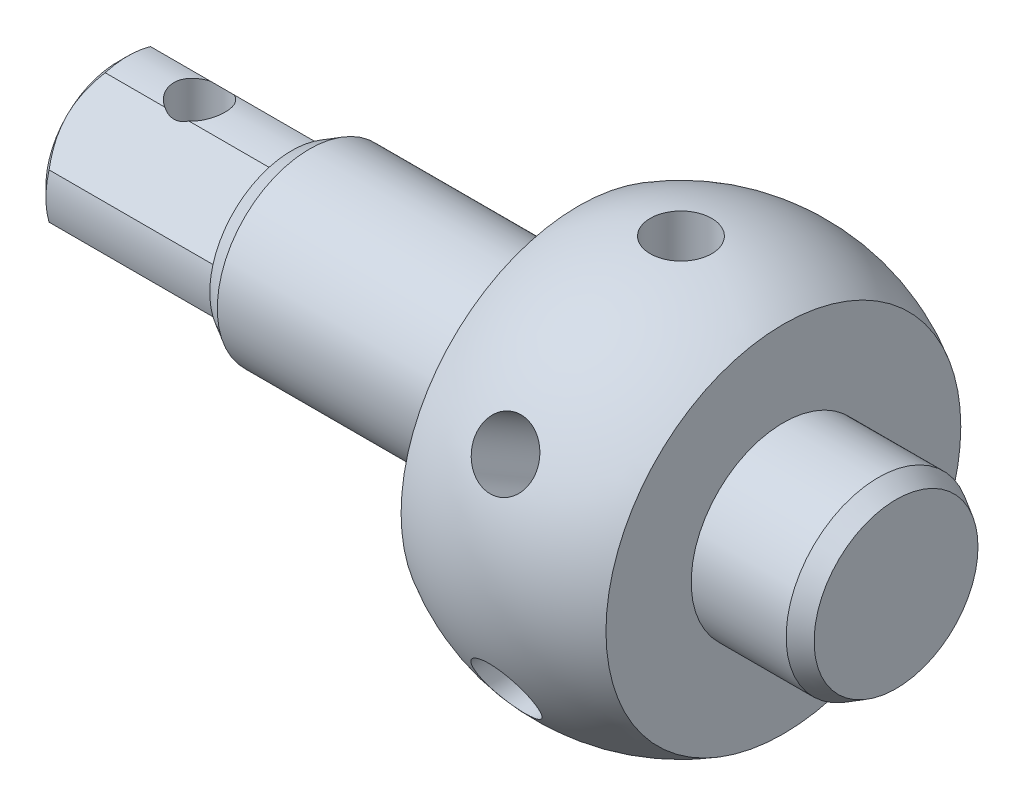
SolidWorks part; units mm, degrees
material "Простая углеродистая сталь"
ref_plane "Спереди" through (0, 0, 0) normal (0, 0, 1) x (1, 0, 0)
ref_plane "Сверху" through (0, 0, 0) normal (0, 1, 0) x (1, 0, 0)
ref_plane "Справа" through (0, 0, 0) normal (1, 0, 0) x (0, 0, -1)
sketch "Эскиз1" plane through (0, 0, 0) normal (0, 0, 1) x (1, 0, 0)
  line L0 (0, 0) -> (-88.2046, 0) construction
  line L1 (0, 0) -> (0, 8)
  line L2 (0, 8) -> (-1.7321, 9)
  line L3 (-1.7321, 9) -> (-11, 9)
  line L4 (-11, 9) -> (-11, 17.3205)
  line L5 (-31, 17.3205) -> (-31, 9)
  line L6 (-31, 9) -> (-57.2679, 9)
  line L7 (-57.2679, 9) -> (-59, 8)
  line L8 (-59, 8) -> (-75, 8)
  line L9 (-76, 7) -> (-76, 0)
  line L10 (-76, 0) -> (0, 0)
  line L11 (-75, 8) -> (-76, 7)
  arc A0 (-31, 17.3205) -> (-11, 17.3205) centre (-21, 0) cw
  point P12 (-76, 8)
  dimension "D6" = 40
  dimension "D1" = 18
  dimension "D2" = 16
  dimension "D3" = 30
  dimension "D4" = 11
  dimension "D5" = 20
  dimension "D7" = 30
  dimension "D8" = 16
  dimension "D9" = 17
  dimension "D10" = 76
  dimension "D11" = 1
  dimension "D12" = 45
revolve "Повернуть1" add sketch "Эскиз1" angle 360 about L0
sketch "Эскиз2" plane through (0, 0, 0) normal (0, 0, 1) x (1, 0, 0)
  line L0 (-11, -17.3205) -> (-11, 17.3205) construction
  circle A0 centre (-21, -10) radius 3
  dimension "D2" = 10
  dimension "D3" = 6
  dimension "D1" = 10
extrude "Вырез-Вытянуть1" cut sketch "Эскиз2" against normal through all and the other way through all
sketch "Эскиз3" plane through (0, 0, 0) normal (0, 0, 1) x (1, 0, 0)
  line L0 (-21, 20) -> (-21, 0) construction
  arc A0 (-11, 17.3205) -> (-31, 17.3205) centre (-21, 0) ccw construction
ref_plane "Плоскость1" through (-21, 20, 0) normal (0, -1, 0) x (-1, 0, 0)
hole_wizard "Диаметр отверстия Ø6.0 (6)1" positions "Эскиз5" profile "Эскиз4" hole size "Ø6.0" standard "Ansi Metric"
sketch "Эскиз5" plane through (-21, 20, 0) normal (0, -1, 0) x (-1, 0, 0)
  point P0 (0, 0)
sketch "Эскиз4" plane through (-21, 20, 0) normal (1, 0, 0) x (0, 0, 1)
  line L0 (0, 0) -> (0, 21.8026)
  line L1 (0, 21.8026) -> (3, 20)
  line L2 (3, 20) -> (3, 0)
  line L5 (3, 0) -> (0, 0)
  line L10 (0, 21.8026) -> (-3, 20) construction
  line L11 (0, -6.35) -> (0, 107.95) construction
  dimension "Диаметр отверстия" = 6
  dimension "Глубина отверстия" = 20
  dimension "Угол заточки сверла" = 118
pattern_circular "Круговой массив1" count 2 every 60 about axis through (0, 0, 0) along (1, 0, 0) of "Диаметр отверстия Ø6.0 (6)1"
sketch "Эскиз6" plane through (-76, 0, 0) normal (-1, 0, 0) x (0, 0, 1)
  line L0 (-9.8995, 0) -> (0, 9.8995)
  line L1 (-9.8995, 0) -> (0, -9.8995)
  line L2 (0, 9.8995) -> (9.8995, 0)
  line L3 (0, -9.8995) -> (9.8995, 0)
  line L4 (-9.8995, 0) -> (9.8995, 0) construction
  line L5 (0, 9.8995) -> (0, -9.8995) construction
  point P1 (0, 0)
  dimension "D1" = 14
extrude "Вырез-Вытянуть2" cut sketch "Эскиз6" against normal blind 17 flip side to cut
ref_plane "Плоскость3" through (0, 10, 0) normal (0, 1, 0) x (1, 0, 0)
hole_wizard "Отверстие обработанное метчиком M61" positions "Эскиз10" profile "Эскиз9" tap size "M6" standard "Iso" end condition through all
sketch "Эскиз10" plane through (0, 10, 0) normal (0, 1, 0) x (1, 0, 0)
  line L0 (-76, 4.9497) -> (-76, -4.9497) construction
  point P0 (-68, 0)
  dimension "D1" = 8
sketch "Эскиз9" plane through (-68, 10, 0) normal (1, 0, 0) x (0, 0, 1)
  line L0 (0, 0) -> (0, 30)
  line L1 (0, 30) -> (2.5, 30)
  line L2 (2.5, 30) -> (2.5, 0)
  line L5 (2.5, 0) -> (0, 0)
  line L11 (0, -6.35) -> (0, 107.95) construction
  dimension "Диаметр проходного сверла" = 5
  dimension "Глубина проходного сверла" = 30
cosmetic thread "Отверстие резьбы1" parameters "D2"=6
sketch "Эскиз11" plane through (0, 10, 0) normal (0, 1, 0) x (1, 0, 0)
  line L0 (-76, 0.5) -> (-75.5, 0)
  line L1 (-75.5, 0) -> (-76, -0.5)
  line L2 (-76, -0.5) -> (-76, 0.5)
  line L3 (-76, 4.9497) -> (-76, -4.9497) construction
  dimension "D1" = 1
extrude "Вырез-Вытянуть3" cut sketch "Эскиз11" against normal up to surface (10 mm away)
